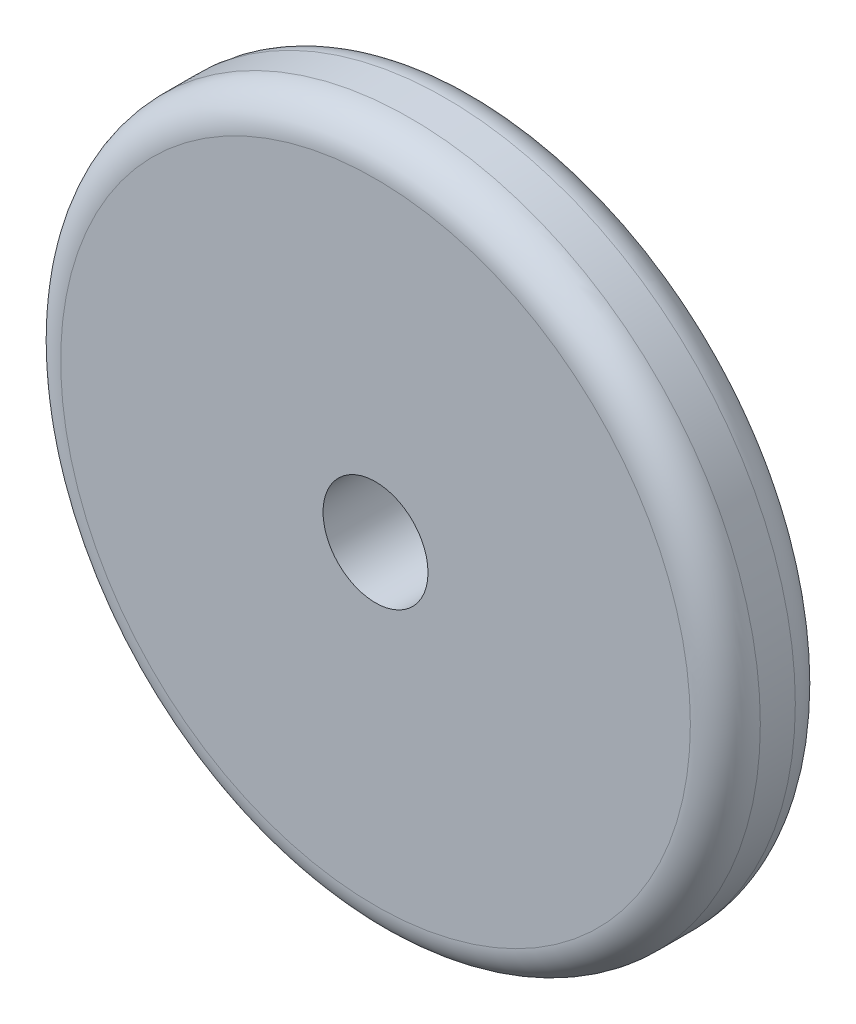
SolidWorks part; units mm, degrees
ref_plane "Front Plane" through (0, 0, 0) normal (0, 0, 1) x (1, 0, 0)
ref_plane "Top Plane" through (0, 0, 0) normal (0, 1, 0) x (1, 0, 0)
ref_plane "Right Plane" through (0, 0, 0) normal (1, 0, 0) x (0, 0, -1)
sketch "Sketch1" plane through (0, 0, 0) normal (0, 0, 1) x (1, 0, 0)
  circle A0 centre (0, 0) radius 10
  circle A1 centre (0, 0) radius 1.5
  dimension "D1" = 20
  dimension "D2" = 3
extrude "Boss-Extrude1" add sketch "Sketch1" along normal blind 3
fillet "Fillet1" radius 1 2 edges at (10, 0, 0) (10, 0, 3)
